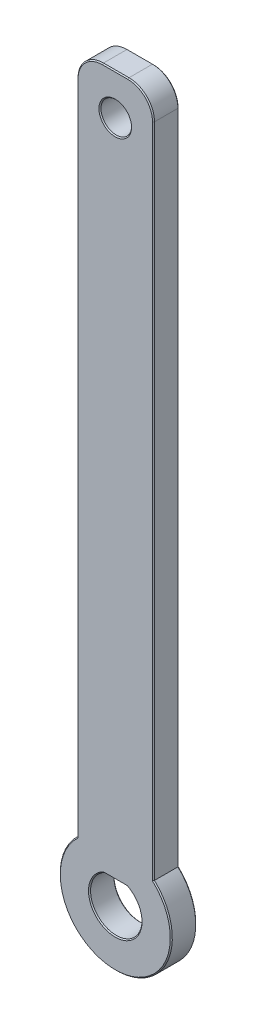
SolidWorks part; units mm, degrees
ref_plane "前视基准面" through (0, 0, 0) normal (0, 0, 1) x (1, 0, 0)
ref_plane "上视基准面" through (0, 0, 0) normal (0, 1, 0) x (1, 0, 0)
ref_plane "右视基准面" through (0, 0, 0) normal (1, 0, 0) x (0, 0, -1)
other "Configuration Table"
sketch "草图1" plane through (0, 0, 0) normal (0, 0, 1) x (1, 0, 0)
  line L1 (0, 0) -> (30, 0)
  line L2 (0, 0) -> (0, -300)
  line L3 (0, -300) -> (30, -300)
  line L4 (30, 0) -> (30, -300)
  dimension "D1" = 300
  dimension "D2" = 30
extrude "凸台-拉伸1" add sketch "草图1" along normal blind 10
sketch "草图2" plane through (0, 0, 10) normal (0, 0, 1) x (1, 0, 0)
  line L0 (0, -300) -> (30, -300) construction
  circle A0 centre (15, -284) radius 10.1
  dimension "D1" = 20.2
  dimension "D2" = 16
extrude "切除-拉伸1" cut sketch "草图2" against normal blind 10
sketch "草图3" plane through (0, 0, 10) normal (0, 0, 1) x (1, 0, 0)
  line L0 (30, 0) -> (0, 0) construction
  circle A0 centre (15, -16) radius 6
  point P4 (15, 0)
  dimension "D2" = 12
  dimension "D1" = 16
  dimension "D3" = 0
extrude "切除-拉伸2" cut sketch "草图3" against normal blind 10
sketch "草图4" plane through (0, 0, 10) normal (0, 0, 1) x (1, 0, 0)
  line L0 (10.4163, -275) -> (19.5837, -275)
  arc A0 (19.5837, -275) -> (10.4163, -275) centre (15, -284) ccw
  dimension "D1" = 20.2
  dimension "D2" = 9
extrude "凸台-拉伸2" add sketch "草图4" against normal up to surface (10 mm away) up to face at (21, -16, 0)
sketch "草图5" plane through (0, 0, 0) normal (0, 0, -1) x (-1, 0, 0)
  circle A0 centre (-15, -284) radius 10.1
  circle A1 centre (-15, -284) radius 22
  dimension "D1" = 44
extrude "凸台-拉伸3" add sketch "草图5" against normal blind 10
fillet "圆角1" radius 10 2 edges at (30, 0, 5) (0, 0, 5)
chamfer "倒角1" distance 0.4 angle 45 18 edges at (15, -294.1, 10) (15, -275, 10) (21, -16, 10) (15, -306, 10) (0, -138.9533, 10) (2.9289, -2.9289, 10) (15, 0, 10) (27.0711, -2.9289, 10) (30, -138.9533, 10) (15, -294.1, 0) (15, -275, 0) (21, -16, 0) (2.9289, -2.9289, 0) (0, -138.9533, 0) (15, -306, 0) (30, -138.9533, 0) (27.0711, -2.9289, 0) (15, 0, 0)
